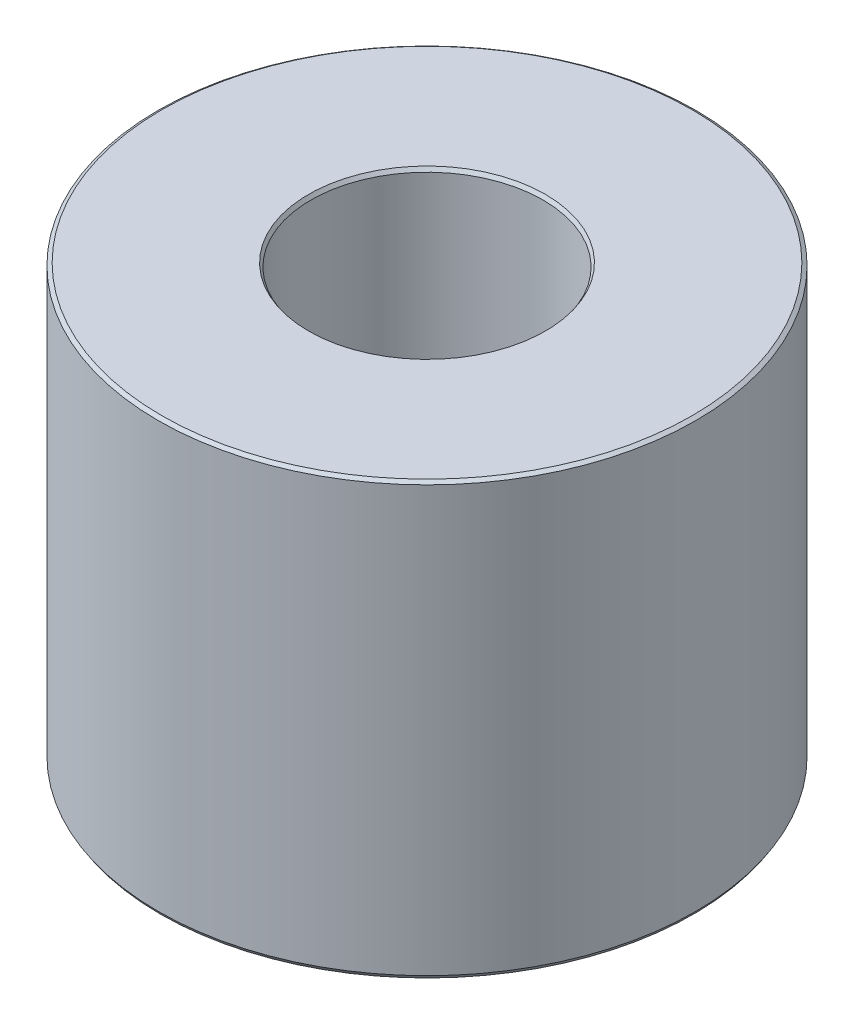
SolidWorks part; units mm, degrees
ref_plane "Front Plane" through (0, 0, 0) normal (0, 0, 1) x (1, 0, 0)
ref_plane "Top Plane" through (0, 0, 0) normal (0, 1, 0) x (1, 0, 0)
ref_plane "Right Plane" through (0, 0, 0) normal (1, 0, 0) x (0, 0, -1)
sketch "Sketch1" plane through (0, 0, 0) normal (0, 1, 0) x (1, 0, 0)
  circle A0 centre (0, 0) radius 57.5
  dimension "SLEEVE_OD" = 115
extrude "Boss-Extrude1" add sketch "Sketch1" along normal blind 92.2312
sketch "Sketch2" plane through (0, 0, 0) normal (0, 1, 0) x (1, 0, 0)
  circle A0 centre (0, 0) radius 24.8305
  dimension "BORE_D" = 49.6609
extrude "Cut-Extrude1" cut sketch "Sketch2" along normal through all
chamfer "Chamfer1" distance 0.5073 angle 57.193 4 edges at (0, 92.2312, 24.8305) (0, 0, 24.8305) (0, 0, 57.5) (0, 92.2312, 57.5) first distance on face at (0, 92.2312, 24.8305) first distance on face at (0, 0, 24.8305) first distance on face at (0, 92.2312, 57.5)
